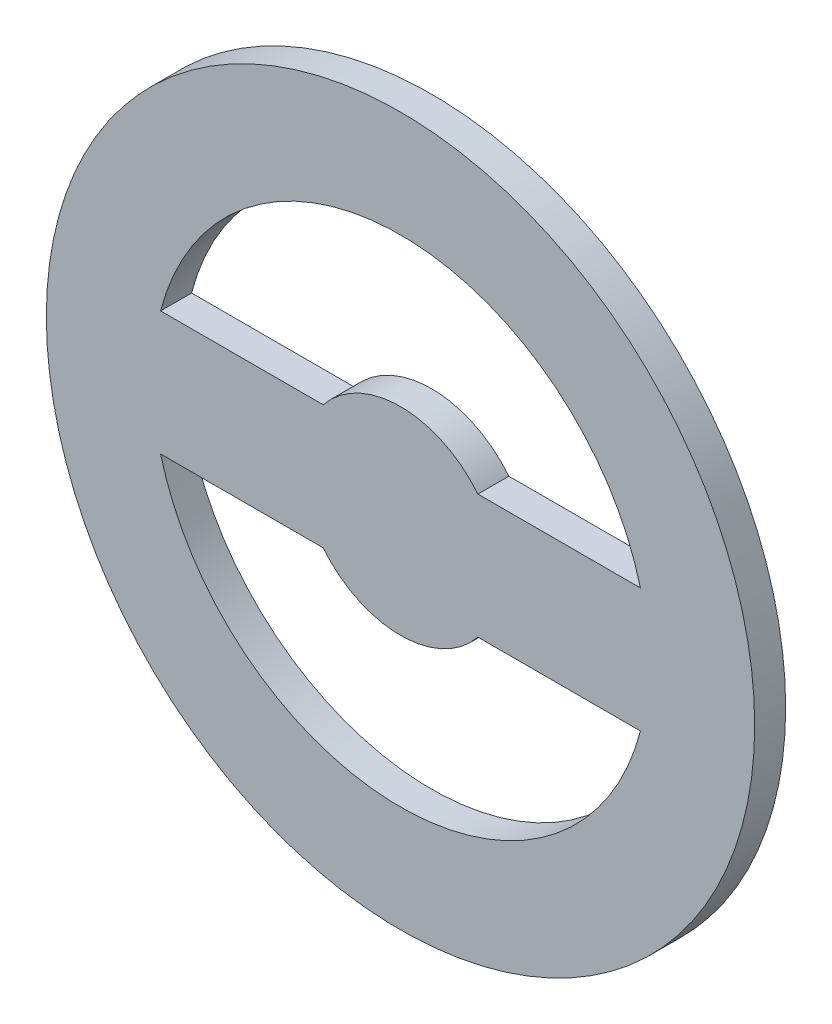
SolidWorks part; units mm, degrees
ref_plane "Front Plane" through (0, 0, 0) normal (0, 0, 1) x (1, 0, 0)
ref_plane "Top Plane" through (0, 0, 0) normal (0, 1, 0) x (1, 0, 0)
ref_plane "Right Plane" through (0, 0, 0) normal (1, 0, 0) x (0, 0, -1)
sketch "Sketch1" plane through (0, 0, 0) normal (0, 0, 1) x (1, 0, 0)
  circle A0 centre (0, 0) radius 36.3093
  dimension "D1" = 72.6186
extrude "Boss-Extrude1" add sketch "Sketch1" along normal blind 3.175
sketch "Sketch2" plane through (0, 0, 3.175) normal (0, 0, 1) x (1, 0, 0)
  line L0 (-24.5934, -6.35) -> (-7.9311, -6.35)
  line L1 (7.9311, 6.35) -> (24.5934, 6.35)
  line L2 (7.9311, -6.35) -> (24.5934, -6.35)
  line L3 (-24.5934, 6.35) -> (-7.9311, 6.35)
  line L4 (-24.5934, -6.35) -> (24.5934, 6.35) construction
  line L5 (24.5934, -6.35) -> (-24.5934, 6.35) construction
  arc A0 (7.9311, 6.35) -> (-7.9311, 6.35) centre (0, 0) ccw
  arc A1 (-24.5934, -6.35) -> (24.5934, -6.35) centre (0, 0) ccw
  arc A2 (24.5934, 6.35) -> (-24.5934, 6.35) centre (0, 0) ccw
  arc A3 (-7.9311, -6.35) -> (7.9311, -6.35) centre (0, 0) ccw
  point P9 (0, 0)
  dimension "D1" = 20.32
  dimension "D2" = 50.8
  dimension "D3" = 12.7
extrude "Cut-Extrude1" cut sketch "Sketch2" against normal through all
